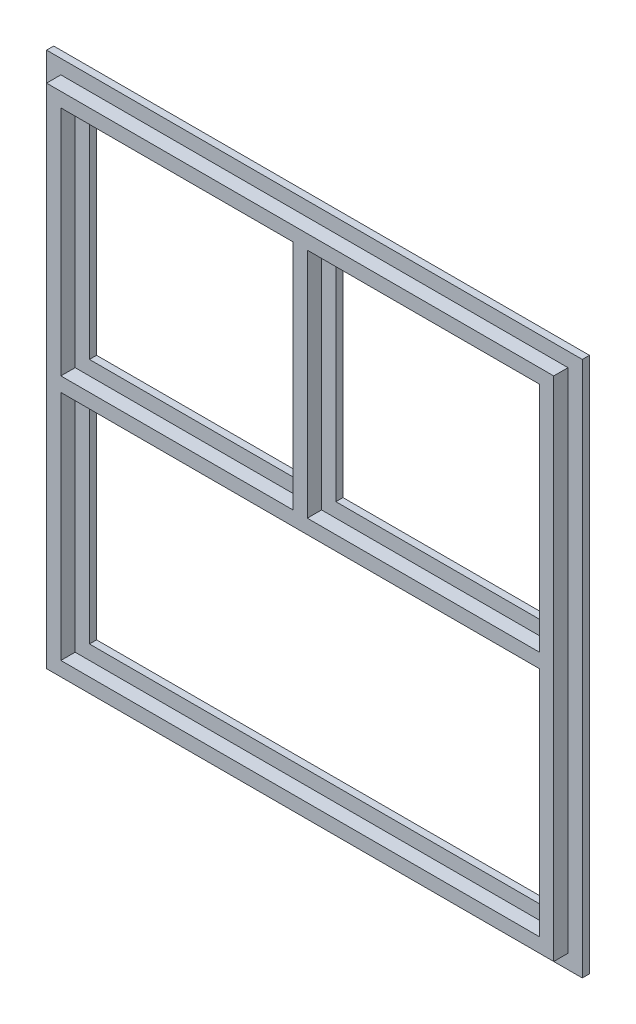
SolidWorks part; units mm, degrees
ref_plane "Plano frontal" through (0, 0, 0) normal (0, 0, 1) x (1, 0, 0)
ref_plane "Plano superior" through (0, 0, 0) normal (0, 1, 0) x (1, 0, 0)
ref_plane "Plano direito" through (0, 0, 0) normal (1, 0, 0) x (0, 0, -1)
sketch "Esboço1" plane through (0, 0, 0) normal (0, 0, 1) x (1, 0, 0)
  line L1 (-37.5, -37.5) -> (37.5, -37.5)
  line L2 (-37.5, -37.5) -> (-37.5, 37.5)
  line L3 (-37.5, 37.5) -> (37.5, 37.5)
  line L4 (37.5, -37.5) -> (37.5, 37.5)
  line L5 (-37.5, -37.5) -> (37.5, 37.5) construction
  line L6 (-37.5, 37.5) -> (37.5, -37.5) construction
  point P0 (0, 0)
  dimension "D1" = 75
  dimension "D2" = 75
extrude "Ressalto-extrusão1" add sketch "Esboço1" along normal blind 1
sketch "Esboço2" plane through (0, 0, 1) normal (0, 0, 1) x (1, 0, 0)
  line L1 (-35.5, -35.5) -> (35.5, -35.5)
  line L2 (-35.5, -35.5) -> (-35.5, 35.5)
  line L3 (-35.5, 35.5) -> (35.5, 35.5)
  line L4 (35.5, -35.5) -> (35.5, 35.5)
  line L5 (-35.5, -35.5) -> (35.5, 35.5) construction
  line L6 (-35.5, 35.5) -> (35.5, -35.5) construction
  line L7 (-33.5, -33.5) -> (33.5, -33.5)
  line L8 (-33.5, -33.5) -> (-33.5, 33.5)
  line L9 (-33.5, 33.5) -> (33.5, 33.5)
  line L10 (33.5, -33.5) -> (33.5, 33.5)
  line L11 (-33.5, -33.5) -> (33.5, 33.5) construction
  line L12 (-33.5, 33.5) -> (33.5, -33.5) construction
  point P0 (0, 0)
  point P6 (0, 0)
  dimension "D1" = 71
  dimension "D2" = 71
  dimension "D3" = 2
  dimension "D4" = 2
extrude "Ressalto-extrusão2" add sketch "Esboço2" along normal blind 2
sketch "Esboço3" plane through (0, 0, 1) normal (0, 0, 1) x (1, 0, 0)
  line L0 (-33.5, 33.5) -> (-33.5, -33.5) construction
  line L1 (3, 14.75) -> (3, 3)
  line L2 (33.5, -33.5) -> (33.5, 33.5) construction
  line L3 (3, 3) -> (15.75, 3)
  line L4 (0, -3) -> (0, 32.5)
  line L6 (33.5, 33.5) -> (-33.5, 33.5) construction
  line L7 (3, 3) -> (31.5, 3)
  line L8 (0, -3) -> (31.5, -3)
  line L9 (15.75, -3) -> (15.75, 3)
  line L10 (3, 3) -> (3, 31.5)
  line L11 (3, 31.5) -> (31.5, 31.5)
  line L16 (-33.5, -33.5) -> (33.5, -33.5) construction
  line L21 (-31.5, -3) -> (31.5, -3)
  line L22 (-31.5, -3) -> (-31.5, -31.5)
  line L23 (-31.5, -31.5) -> (31.5, -31.5)
  line L24 (31.5, -3) -> (31.5, -31.5)
  line L26 (0, 14.75) -> (3, 14.75)
  line L27 (0, 14.75) -> (-3, 14.75)
  line L28 (-31.5, -3) -> (0, -3)
  line L29 (-31.5, -3) -> (0, -3)
  line L30 (-17.25, 3) -> (-17.25, -3)
  line L31 (31.5, 3) -> (31.5, 31.5)
  line L32 (-3, 3) -> (-31.5, 3)
  line L33 (-3, 3) -> (-3, 31.5)
  line L34 (-3, 31.5) -> (-31.5, 31.5)
  line L35 (-31.5, 3) -> (-31.5, 31.5)
  dimension "D2" = 2
  dimension "D3" = 2
  dimension "D4" = 3
  dimension "D5" = 3
  dimension "D6" = 6
  dimension "D7" = 2
  dimension "D8" = 2
  dimension "D9" = 2
  dimension "D10" = 2
  dimension "D11" = 2
  dimension "D12" = 28.5
  dimension "D13" = 6
extrude "Corte-extrusão2" cut sketch "Esboço3" against normal blind 3 contours L24 L21 L22 L23 | L33 L32 L35 L34 | L10 L7 L31 L11 region at (0, -17.25, 1)
sketch "Esboço4" plane through (0, 0, 1) normal (0, 0, 1) x (1, 0, 0)
  line L0 (-33.5, 33.5) -> (33.5, 33.5)
  line L3 (33.5, -33.5) -> (33.5, 33.5) construction
  line L5 (-33.5, 33.5) -> (-33.5, -33.5) construction
  line L6 (-33.5, 0) -> (-33.5, 1)
  line L7 (-33.5, 0) -> (-33.5, -1)
  line L8 (-33.5, 33.5) -> (-33.5, -33.5) construction
  line L9 (0, 33.5) -> (-1, 33.5)
  line L10 (0, 33.5) -> (1, 33.5)
  line L11 (33.5, 0) -> (33.5, 1)
  line L12 (33.5, -33.5) -> (33.5, 33.5) construction
  line L13 (33.5, 0) -> (33.5, -1)
  line L14 (33.5, 1) -> (1, 1)
  line L15 (1, 1) -> (1, 33.5)
  line L16 (-1, 33.5) -> (-1, 1)
  line L17 (-1, 1) -> (-33.5, 1)
  line L18 (-33.5, -1) -> (33.5, -1)
  line M10 (33.5, -33.5) -> (33.5, 33.5)
  line M12 (-33.5, 33.5) -> (-33.5, -33.5)
  dimension "D1" = 1
  dimension "D2" = 1
  dimension "D3" = 1
  dimension "D4" = 1
  dimension "D5" = 1
  dimension "D6" = 1
extrude "Ressalto-extrusão3" add sketch "Esboço4" along normal blind 2 contours L18 L14 L15 L0 L16 L17 M12 M10 region at (0, 5.6344, 1)
